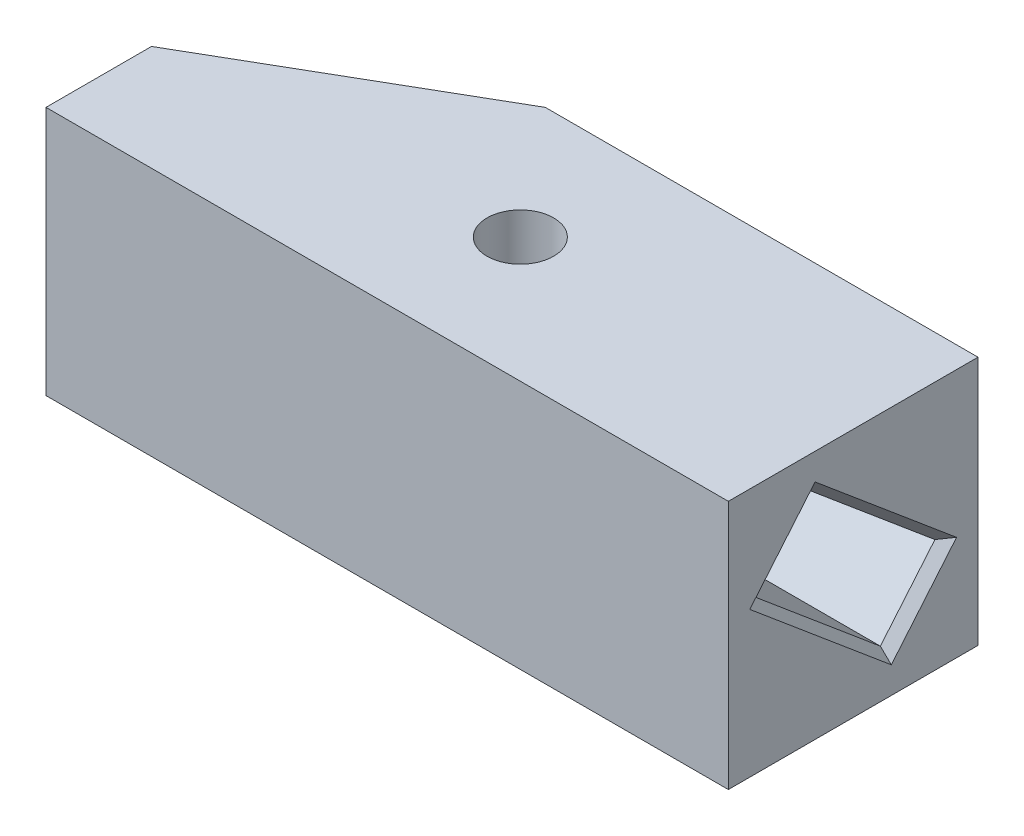
SolidWorks part; units mm, degrees
ref_plane "Спереди" through (0, 0, 0) normal (0, 0, 1) x (1, 0, 0)
ref_plane "Сверху" through (0, 0, 0) normal (0, 1, 0) x (1, 0, 0)
ref_plane "Справа" through (0, 0, 0) normal (1, 0, 0) x (0, 0, -1)
sketch "Эскиз1" plane through (0, 0, 0) normal (0, 1, 0) x (1, 0, 0)
  line L0 (-20, -15) -> (-35, -15)
  line L1 (-20, -15) -> (20, -15)
  line L2 (-35, -15) -> (-35, 15)
  line L3 (-20, 15) -> (20, 15)
  line L4 (20, -15) -> (20, 15)
  line L5 (-20, -15) -> (20, 15) construction
  line L6 (-20, 15) -> (20, -15) construction
  line L7 (-35, 15) -> (-20, 15)
  point P0 (0, 0)
  dimension "D1" = 40
  dimension "D2" = 30
  dimension "D3" = 15
extrude "Бобышка-Вытянуть1" add sketch "Эскиз1" along normal blind 30
sketch "Эскиз2" plane through (0, 30, 0) normal (0, 1, 0) x (1, 0, 0)
  line L0 (-20, -15) -> (-20, 15) construction
  circle A0 centre (-20, 0) radius 4
  dimension "D1" = 15
extrude "Вырез-Вытянуть1" cut sketch "Эскиз2" against normal through all
sketch "Эскиз5" plane through (20, 0, 0) normal (1, 0, 0) x (0, 0, -1)
  line L0 (0, 30) -> (0, 0) construction
  line L1 (-15, 30) -> (15, 0) construction
  line L2 (-15, 0) -> (15, 0) construction
  line L4 (4.4588, 4.601) -> (11.0153, 12.4147)
  line L5 (4.4588, 4.601) -> (-11.0153, 17.5853)
  line L6 (-11.0153, 17.5853) -> (-4.4588, 25.399)
  line L7 (11.0153, 12.4147) -> (-4.4588, 25.399)
  line L8 (4.4588, 4.601) -> (-4.4588, 25.399) construction
  line L9 (-11.0153, 17.5853) -> (11.0153, 12.4147) construction
  point P5 (0, 15)
  point P6 (0, 15)
  dimension "D1" = 20.2
  dimension "D2" = 10.2
  dimension "D3" = 40
extrude "Вырез-Вытянуть4" cut sketch "Эскиз5" against normal blind 25
sketch "Sketch1" plane through (-35, 0, 0) normal (-1, 0, 0) x (0, 0, 1)
  line L0 (0, 30) -> (0, 0) construction
  line L1 (-15, 30) -> (15, 30) construction
  line L3 (-15, 0) -> (15, 0)
  line L4 (-15, 0) -> (-15, 30)
  line L5 (-15, 30) -> (15, 30)
  line L6 (15, 0) -> (15, 30)
  line L7 (-15, 0) -> (15, 30) construction
  line L8 (-15, 30) -> (15, 0) construction
  point P5 (0, 15)
extrude "Boss-Extrude1" add sketch "Sketch1" along normal blind 27
chamfer "Chamfer1" distance 30 angle 30 1 edges at (-62, 15, -15) first distance on face at (-21, 15, -15)
chamfer "Chamfer2" distance 1 angle 50 4 edges at (20, 8.5078, -7.737) (20, 18.9068, -3.2782) (20, 21.4922, 7.737) (20, 11.0932, 3.2782) first distance on face at (20, 15, 0)
